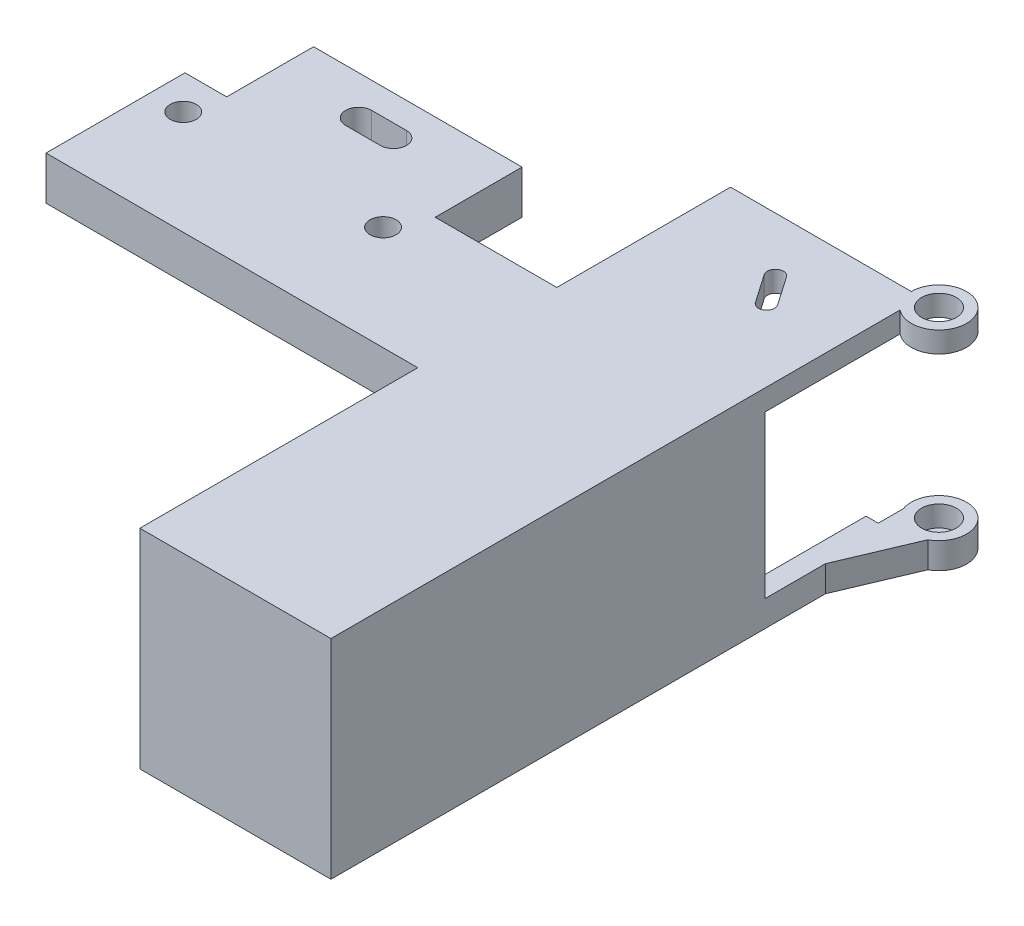
SolidWorks part; units mm, degrees
ref_plane "Front Plane" through (0, 0, 0) normal (0, 0, 1) x (1, 0, 0)
ref_plane "Top Plane" through (0, 0, 0) normal (0, 1, 0) x (1, 0, 0)
ref_plane "Right Plane" through (0, 0, 0) normal (1, 0, 0) x (0, 0, -1)
sketch "Sketch1" plane through (0, 0, 0) normal (0, 1, 0) x (1, 0, 0)
  line L0 (0, 0) -> (0, 40)
  line L1 (0, 40) -> (12, 40)
  line L2 (12, 40) -> (12, 65)
  line L3 (12, 65) -> (72, 65)
  line L4 (72, 65) -> (72, 40)
  line L5 (72, 40) -> (107, 40)
  line L6 (107, 40) -> (107, 0)
  line L7 (107, 0) -> (0, 0)
  dimension "D1" = 40
  dimension "D2" = 12
  dimension "D3" = 60
  dimension "D4" = 25
  dimension "D5" = 35
extrude "Boss-Extrude1" add sketch "Sketch1" along normal blind 12.5
sketch "Sketch2" plane through (0, 12.5, 0) normal (0, 1, 0) x (1, 0, 0)
  line L0 (107, 0) -> (107, 40) construction
  line L1 (107, 0) -> (107, 40)
  line L2 (107, 40) -> (107, 90)
  line L3 (107, 90) -> (162, 90)
  line L4 (162, 90) -> (162, -80)
  line L5 (162, -80) -> (107, -80)
  line L6 (107, -80) -> (107, 0)
  dimension "D1" = 55
  dimension "D2" = 50
  dimension "D3" = 170
extrude "Boss-Extrude2" add sketch "Sketch2" against normal blind 60
sketch "Sketch3" plane through (0, 0, -90) normal (0, 0, -1) x (-1, 0, 0)
  line L8 (-109.5, 10) -> (-159.5, 10)
  line L9 (-159.5, 10) -> (-159.5, -45)
  line L10 (-159.5, -45) -> (-109.5, -45)
  line L11 (-109.5, -45) -> (-109.5, 10)
  line L12 (-109.5, 10) -> (-159.5, 10)
  line L13 (-159.5, 10) -> (-159.5, -45)
  line L14 (-159.5, -45) -> (-109.5, -45)
  line L15 (-109.5, -45) -> (-109.5, 10)
  dimension "D1" = 2.5
extrude "Cut-Extrude1" cut sketch "Sketch3" against normal blind 167.5
fillet "Fillet1" radius 2.5 1 edges at (134.5, -45, -90) second distance 10 first distance on face at (134.5, -17.5, -90)
sketch "Sketch6" plane through (0, 12.5, 0) normal (0, 1, 0) x (1, 0, 0)
  line L0 (162, 90) -> (107, 90) construction
  line L1 (162, -80) -> (162, 90) construction
  circle A0 centre (166.966, 90) radius 7.9518
  dimension "D1" = 4.966
  dimension "D2" = 15.9036
extrude "Boss-Extrude3" add sketch "Sketch6" against normal up to surface (60 mm away) up to face at (139.0833, -47.5, -33.3333)
ref_plane "Plane1" through (0, 10, 0) normal (0, 1, 0) x (1, 0, 0)
sketch "Sketch7" plane through (0, 10, 0) normal (0, 1, 0) x (1, 0, 0)
  arc A0 (162, 83.7895) -> (159.0142, 90) centre (166.966, 90) ccw construction
  arc A1 (162, 83.7895) -> (159.0142, 90) centre (166.966, 90) ccw
  arc A2 (159.0142, 90) -> (162, 83.7895) centre (166.966, 90) ccw
extrude "Cut-Extrude2" cut sketch "Sketch7" against normal up to surface (55 mm away) up to face at (140.75, -45, 38.125)
sketch "Sketch9" plane through (162, 0, 0) normal (1, 0, 0) x (0, 0, -1)
  line L0 (90.7048, 10) -> (-90.7048, 10) construction
  line L1 (82.2134, 10) -> (87.2632, 10)
  line L2 (82.2134, 10) -> (82.2134, -45)
  line L3 (82.2134, -45) -> (87.2632, -45)
  line L4 (87.2632, 10) -> (87.2632, -45)
  dimension "D1" = 5.0498
extrude "Cut-Extrude3" cut sketch "Sketch9" against normal up to surface (2.5 mm away) up to face at (159.5, -22.2136, -18.6119)
sketch "Sketch10" plane through (0, 12.5, 0) normal (0, 1, 0) x (1, 0, 0)
  circle A0 centre (166.966, 90) radius 5
  dimension "D1" = 10
extrude "Cut-Extrude4" cut sketch "Sketch10" against normal blind 58.5
sketch "Sketch11" plane through (162, 0, 0) normal (1, 0, 0) x (0, 0, -1)
  line L0 (-77.5, 10) -> (90, 10) construction
  line L1 (62.3134, 10) -> (82.3134, 10)
  line L2 (62.3134, 10) -> (62.3134, -45)
  line L3 (62.3134, -45) -> (82.3134, -45)
  line L4 (82.3134, 10) -> (82.3134, -45)
  line L5 (97.9518, -45) -> (82.0482, -45) construction
  line L6 (82.2134, 10) -> (82.2134, -45) construction
  dimension "D1" = 20
  dimension "D2" = 0.1
extrude "Cut-Extrude6" cut sketch "Sketch11" against normal up to surface (2.5 mm away) up to face at (159.5, -29.3974, -26.9764)
sketch "Sketch12" plane through (0, 0, -90) normal (0, 0, -1) x (-1, 0, 0)
  line L1 (-109.5, -45) -> (-159.1154, -45)
  line L2 (-109.5, -45) -> (-109.5, -49.4691)
  line L3 (-109.5, -49.4691) -> (-159.1154, -49.4691)
  line L4 (-159.1154, -45) -> (-159.1154, -49.4691)
  dimension "D1" = 4.4691
  dimension "D2" = 49.6154
extrude "Cut-Extrude7" cut sketch "Sketch12" against normal up to surface (167.5 mm away) up to face at (134.5, -17.5, 77.5)
sketch "Sketch13" plane through (0, -45, 0) normal (0, 1, 0) x (1, 0, 0)
  arc A0 (162, 83.7895) -> (159.0142, 90) centre (166.966, 90) ccw construction
  arc A1 (162, 83.7895) -> (159.0142, 90) centre (166.966, 90) ccw
  arc A2 (162, 83.7895) -> (159.0142, 90) centre (166.966, 90) cw
  circle A3 centre (166.966, 90) radius 5 construction
  circle A4 centre (166.966, 90) radius 5
extrude "Boss-Extrude4" add sketch "Sketch13" along normal blind 5
sketch "Sketch15" plane through (0, -45, 0) normal (0, 1, 0) x (1, 0, 0)
  line L0 (162, 62.3134) -> (162, 83.7895) construction
  line L1 (162, 62.3134) -> (162, 83.7895)
  line L2 (162, 62.3134) -> (170.7606, 83.012)
  arc A0 (162, 83.7895) -> (159.0142, 90) centre (166.966, 90) ccw construction
  arc A1 (162, 83.7895) -> (170.7606, 83.012) centre (166.966, 90) ccw
  dimension "D1" = 22.4762
extrude "Boss-Extrude5" add sketch "Sketch15" against normal up to surface (2.5 mm away) up to face at (137.4487, -47.5, -4.6594)
sketch "Sketch17" plane through (109.5, 0, 0) normal (1, 0, 0) x (0, 0, -1)
  line L4 (90, -47.5) -> (90, 10)
  line L5 (90, 10) -> (-77.5, 10)
  line L6 (-77.5, 10) -> (-77.5, -47.5)
  line L7 (-77.5, -47.5) -> (90, -47.5)
  line L8 (90, -47.5) -> (90, 10)
  line L9 (90, 10) -> (-77.5, 10)
  line L10 (-77.5, 10) -> (-77.5, -47.5)
  line L11 (-77.5, -47.5) -> (90, -47.5)
  dimension "D1" = 0
extrude "Boss-Extrude6" add sketch "Sketch17" along normal blind 3.5
sketch "Sketch19" plane through (0, 10, 0) normal (0, -1, 0) x (1, 0, 0)
  line L6 (159.5, 77.5) -> (113, 77.5)
  line L7 (113, 77.5) -> (113, -90)
  line L8 (113, -90) -> (159.0142, -90)
  line L9 (162, -83.7895) -> (162, -62.3134)
  line L10 (162, -62.3134) -> (159.5, -62.3134)
  line L11 (159.5, -62.3134) -> (159.5, 77.5)
  line L12 (159.5, 77.5) -> (113, 77.5)
  line L13 (113, 77.5) -> (113, -90)
  line L14 (113, -90) -> (159.0142, -90)
  line L15 (162, -83.7895) -> (162, -62.3134)
  line L16 (162, -62.3134) -> (159.5, -62.3134)
  line L17 (159.5, -62.3134) -> (159.5, 77.5)
  arc A1 (159.0142, -90) -> (162, -83.7895) centre (166.966, -90) ccw
  arc A2 (159.0142, -90) -> (162, -83.7895) centre (166.966, -90) ccw
  dimension "D1" = 0
extrude "Boss-Extrude7" add sketch "Sketch19" along normal blind 3.5
sketch "Sketch20" plane through (159.5, 0, 0) normal (-1, 0, 0) x (0, 0, 1)
  line L4 (77.5, -45) -> (77.5, 6.5)
  line L5 (77.5, 6.5) -> (-62.3134, 6.5)
  line L6 (-62.3134, 6.5) -> (-62.3134, -45)
  line L7 (-62.3134, -45) -> (77.5, -45)
  line L8 (77.5, -45) -> (77.5, 6.5)
  line L9 (77.5, 6.5) -> (-62.3134, 6.5)
  line L10 (-62.3134, 6.5) -> (-62.3134, -45)
  line L11 (-62.3134, -45) -> (77.5, -45)
  dimension "D1" = 0
extrude "Boss-Extrude8" add sketch "Sketch20" along normal blind 3.5
sketch "Sketch21" plane through (159.1154, 0, 0) normal (-1, 0, 0) x (0, 0, 1)
  line L7 (-90, -47.5) -> (77.5, -47.5)
  line L8 (77.5, -47.5) -> (77.5, -45)
  line L9 (77.5, -45) -> (-62.3134, -45)
  line L10 (-62.3134, -45) -> (-80, -45)
  line L11 (-88.7357, -46.2832) -> (-88.7357, -45)
  line L12 (-88.7357, -45) -> (-90, -45)
  line L13 (-90, -45) -> (-90, -47.5)
  line L14 (-90, -47.5) -> (77.5, -47.5)
  line L15 (77.5, -47.5) -> (77.5, -45)
  line L16 (77.5, -45) -> (-62.3134, -45)
  line L17 (-62.3134, -45) -> (-80, -45)
  line L18 (-88.7357, -46.2832) -> (-88.7357, -45)
  line L19 (-88.7357, -45) -> (-90, -45)
  line L20 (-90, -45) -> (-90, -47.5)
  spline S1 degree 2 poles (-80, -45) (-85.8758, -45) (-88.7357, -46.2832) knots 0.331688 0.331688 0.331688 1 1 1 weights 1 0.804256 0.870148
  spline S2 degree 2 poles (-80, -45) (-85.8758, -45) (-88.7357, -46.2832) knots 0.331688 0.331688 0.331688 1 1 1 weights 1 0.804256 0.870148
  dimension "D1" = 0
extrude "Boss-Extrude9" add sketch "Sketch21" along normal up to surface (3.1154 mm away) up to face at (156, -19.25, 7.5933)
sketch "Sketch22" plane through (0, -45, 0) normal (0, 1, 0) x (1, 0, 0)
  line L6 (159.5, 80) -> (159.1154, 80)
  line L7 (159.1154, 80) -> (156, 80)
  line L8 (156, 80) -> (156, 62.3134)
  line L9 (156, 62.3134) -> (162, 62.3134)
  line L10 (162, 62.3134) -> (170.7606, 83.012)
  line L11 (159.5, 87.2632) -> (159.5, 80)
  line L12 (159.5, 80) -> (159.1154, 80)
  line L13 (159.1154, 80) -> (156, 80)
  line L14 (156, 80) -> (156, 62.3134)
  line L15 (156, 62.3134) -> (162, 62.3134)
  line L16 (162, 62.3134) -> (170.7606, 83.012)
  line L17 (159.5, 87.2632) -> (159.5, 80)
  arc A1 (159.5, 87.2632) -> (170.7606, 83.012) centre (166.966, 90) ccw
  arc A2 (159.5, 87.2632) -> (170.7606, 83.012) centre (166.966, 90) ccw
  dimension "D1" = 0
extrude "Boss-Extrude10" add sketch "Sketch22" along normal blind 4
sketch "Sketch24" plane through (0, 12.5, 0) normal (0, 1, 0) x (1, 0, 0)
  line L0 (72, 40) -> (72, 65) construction
  line L1 (107, 40) -> (72, 40) construction
  line L2 (67, 30) -> (-21.6913, 30) construction
  circle A0 centre (67, 30) radius 3.75
  circle A1 centre (9.5, 30) radius 3.75
  dimension "D1" = 5
  dimension "D3" = 7.5
  dimension "D5" = 7.5
  dimension "D2" = 10
  dimension "D4" = 57.5
extrude "Cut-Extrude8" cut sketch "Sketch24" against normal through all
sketch "Sketch25" plane through (0, 12.5, 0) normal (0, 1, 0) x (1, 0, 0)
  line L0 (36.2279, 53.75) -> (46.2279, 53.75) construction
  line L1 (36.2279, 57.5) -> (46.2279, 57.5)
  line L2 (36.2279, 50) -> (46.2279, 50)
  line L3 (72, 65) -> (12, 65) construction
  line L4 (12, 65) -> (12, 40) construction
  arc A0 (36.2279, 57.5) -> (36.2279, 50) centre (36.2279, 53.75) ccw
  arc A1 (46.2279, 50) -> (46.2279, 57.5) centre (46.2279, 53.75) ccw
  point P2 (41.2279, 53.75)
  dimension "D1" = 7.5
  dimension "D2" = 10
  dimension "D3" = 7.5
  dimension "D4" = 24.2279
extrude "Cut-Extrude9" cut sketch "Sketch25" against normal through all
sketch "Sketch26" plane through (0, 10, 0) normal (0, 1, 0) x (1, 0, 0)
  circle A1 centre (166.966, 90) radius 5
  circle A2 centre (166.966, 90) radius 5
  dimension "D1" = 0
extrude "Cut-Extrude10" cut sketch "Sketch26" against normal up to surface (3.5 mm away) up to face at (147.8057, 6.5, -34.281)
sketch "Sketch27" plane through (0, 0, -40) normal (0, 0, -1) x (-1, 0, 0)
  line L0 (-102.3233, 0) -> (-107, -4.6767)
  line L1 (-107, 0) -> (-72, 0) construction
  line L2 (-107, -47.5) -> (-107, 12.5) construction
  line L3 (-107, -4.6767) -> (-107, 0)
  line L4 (-107, 0) -> (-102.3233, 0)
  dimension "D1" = 6.6139
  dimension "D2" = 135
extrude "Boss-Extrude11" add sketch "Sketch27" against normal up to surface (40 mm away) up to face at (53.5, 6.25, 0)
fillet "Fillet2" radius 10 2 edges at (113, 6.5, -6.25) (156, 6.5, 7.5933)
sketch "Sketch28" plane through (0, 12.5, 0) normal (0, 1, 0) x (1, 0, 0)
  line L0 (166.966, 90) -> (136.1151, 68.6817) construction
  line L1 (133.3093, 72.6701) -> (140.8155, 61.8074) construction
  line L2 (159.0142, 90) -> (107, 90) construction
  line L3 (162, -80) -> (162, 83.7895) construction
  line L4 (135.5351, 74.3585) -> (141.2199, 66.1316) construction
  line L5 (137.4272, 75.666) -> (143.1121, 67.4391)
  line L6 (133.6429, 73.051) -> (139.3277, 64.8241)
  circle A0 centre (166.966, 90) radius 3 construction
  arc A1 (137.4272, 75.666) -> (133.6429, 73.051) centre (135.5351, 74.3585) ccw
  arc A2 (139.3277, 64.8241) -> (143.1121, 67.4391) centre (141.2199, 66.1316) ccw
  point P13 (138.3775, 70.245)
  dimension "D1" = 6
  dimension "D2" = 37.5
  dimension "D8" = 2.3
  dimension "D10" = 2.75
  dimension "D3" = 6.2341
  dimension "D4" = 90
  dimension "D5" = 10.8627
  dimension "D6" = 17.3299
  dimension "D7" = 21.1845
  dimension "D9" = 10
extrude "Cut-Extrude11" cut sketch "Sketch28" against normal up to surface (6 mm away) up to face at (166.966, 6.5, -95)
sketch "Sketch30" plane through (162, 0, 0) normal (1, 0, 0) x (0, 0, -1)
  line L0 (62.3134, 6.5) -> (62.3134, -41) construction
  line L1 (62.3134, 6.5) -> (62.3134, -41)
  line L2 (62.3134, 6.5) -> (44.8665, 6.5)
  line L3 (44.8665, 6.5) -> (44.8665, -41)
  line L4 (44.8665, -41) -> (62.3134, -41)
  dimension "D1" = 17.4469
extrude "Cut-Extrude12" cut sketch "Sketch30" against normal blind 15
sketch "Sketch31" plane through (0, -41, 0) normal (0, 1, 0) x (1, 0, 0)
  line L6 (159.5, 87.2632) -> (159.5, 80)
  line L7 (159.5, 80) -> (156, 80)
  line L8 (156, 80) -> (156, 44.8665)
  line L9 (156, 44.8665) -> (162, 44.8665)
  line L10 (162, 44.8665) -> (162, 62.3134)
  line L11 (162, 62.3134) -> (170.7606, 83.012)
  line L12 (159.5, 87.2632) -> (159.5, 80)
  line L13 (159.5, 80) -> (156, 80)
  line L14 (156, 80) -> (156, 44.8665)
  line L15 (156, 44.8665) -> (162, 44.8665)
  line L16 (162, 44.8665) -> (162, 62.3134)
  line L17 (162, 62.3134) -> (170.7606, 83.012)
  arc A1 (159.5, 87.2632) -> (170.7606, 83.012) centre (166.966, 90) ccw
  arc A2 (159.5, 87.2632) -> (170.7606, 83.012) centre (166.966, 90) ccw
  dimension "D1" = 0
extrude "Boss-Extrude12" add sketch "Sketch31" along normal up to surface (1 mm away) up to face at (166.966, -40, -97.9518)
